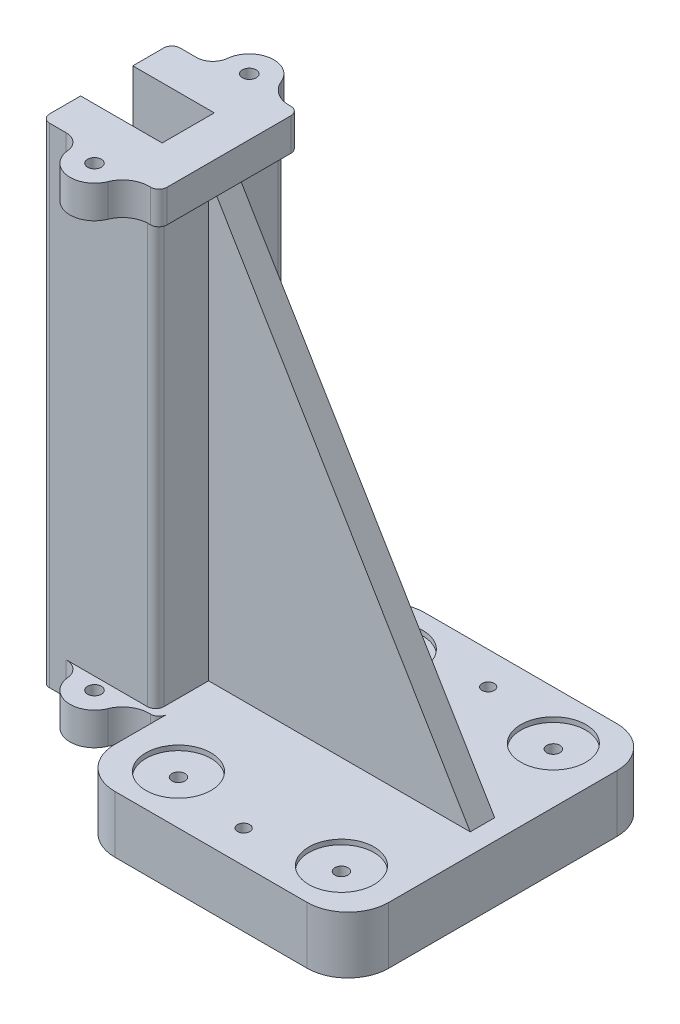
SolidWorks part; units mm, degrees
ref_plane "前视基准面" through (0, 0, 0) normal (0, 0, 1) x (1, 0, 0)
ref_plane "上视基准面" through (0, 0, 0) normal (0, 1, 0) x (1, 0, 0)
ref_plane "右视基准面" through (0, 0, 0) normal (1, 0, 0) x (0, 0, -1)
sketch "草图2" plane through (0, 0, 0) normal (0, 1, 0) x (1, 0, 0)
  line L1 (84, -95) -> (-84, -95)
  line L2 (84, -95) -> (84, 95)
  line L3 (84, 95) -> (-84, 95)
  line L4 (-84, -95) -> (-84, 95)
  line L5 (84, -95) -> (-84, 95) construction
  line L6 (84, 95) -> (-84, -95) construction
  point P0 (0, 0)
  dimension "D1" = 168
  dimension "D2" = 190
extrude "凸台-拉伸1" add sketch "草图2" along normal blind 35
sketch "草图3" plane through (0, 35, 0) normal (0, 1, 0) x (1, 0, 0)
  line L0 (0, 95) -> (0, -95) construction
  line L1 (84, 95) -> (-84, 95) construction
  line L2 (-84, -95) -> (84, -95) construction
  line L3 (-84, 0) -> (84, 0) construction
  line L4 (-84, 95) -> (-84, -95) construction
  line L5 (84, -95) -> (84, 95) construction
  circle A0 centre (0, 75) radius 3.75
  circle A1 centre (0, -75) radius 3.75
  point P16 (0, 0)
  point P17 (0, 0)
  point P18 (0, 0)
  dimension "D1" = 7.5
  dimension "D2" = 150
extrude "切除-拉伸1" cut sketch "草图3" against normal up to next
sketch "草图4" plane through (0, 35, 0) normal (0, 1, 0) x (1, 0, 0)
  line L3 (50, -65) -> (-50, -65) construction
  line L6 (50, -65) -> (50, 65) construction
  line L7 (50, 65) -> (-50, 65) construction
  line L8 (-50, -65) -> (-50, 65) construction
  line L9 (50, -65) -> (-50, 65) construction
  line L10 (50, 65) -> (-50, -65) construction
  circle A4 centre (-50, 65) radius 4
  circle A5 centre (50, 65) radius 4
  circle A6 centre (-50, -65) radius 4
  circle A7 centre (50, -65) radius 4
  point P0 (0, 0)
  dimension "D3" = 8
  dimension "D1" = 130
  dimension "D2" = 100
extrude "切除-拉伸2" cut sketch "草图4" against normal up to next
sketch "草图5" plane through (0, 35, 0) normal (0, 1, 0) x (1, 0, 0)
  circle A0 centre (-50, 65) radius 20
  circle A1 centre (50, 65) radius 20
  circle A2 centre (50, -65) radius 20
  circle A3 centre (-50, -65) radius 20
  dimension "D1" = 40
extrude "切除-拉伸3" cut sketch "草图5" against normal blind 3
fillet "圆角1" radius 25 4 edges at (-84, 17.5, -95) (84, 17.5, -95) (84, 17.5, 95) (-84, 17.5, 95)
ref_plane "基准面1" through (0, 315, 0) normal (0, 1, 0) x (1, 0, 0)
sketch "草图8" plane through (0, 315, 0) normal (0, 1, 0) x (1, 0, 0)
  line L0 (-50, 65) -> (-50, -65) construction
  line L1 (0, 0) -> (-171.4054, 0) construction
  line L2 (-109, -16) -> (-159, -16)
  line L3 (-119, 47.5) -> (-119, -47.5) construction
  line L4 (-109, 16) -> (-109, -16)
  line L5 (-109, 16) -> (-159, 16)
  line L6 (-159, 16) -> (-159, 35)
  line L7 (-84, 70) -> (-84, -70) construction
  line L9 (-84, 38.0172) -> (-84, -38.0172)
  line L13 (-159, -16) -> (-159, -40)
  line L14 (-154, 40) -> (-143.8747, 40)
  line L15 (-143.8747, 40) -> (-74.7829, 40) construction
  line L16 (-154, -40) -> (-143.8747, -40)
  arc A0 (-105.0963, 53.1292) -> (-133.9248, 49) centre (-119, 47.5) ccw
  arc A11 (-159, 35) -> (-154, 40) centre (-154, 35) cw
  arc A12 (-143.8747, 40) -> (-133.9248, 49) centre (-143.8747, 50) ccw
  arc A13 (-84, 38.0172) -> (-89.2482, 43.011) centre (-89, 38.0172) ccw
  arc A14 (-89.2482, 43.011) -> (-105.0963, 53.1292) centre (-90.054, 59.2195) cw
  arc A15 (-84, -38.0172) -> (-89.2482, -43.011) centre (-89, -38.0172) cw
  arc A16 (-89.2482, -43.011) -> (-105.0963, -53.1292) centre (-90.054, -59.2195) ccw
  arc A17 (-105.0963, -53.1292) -> (-133.9248, -49) centre (-119, -47.5) cw
  arc A18 (-143.8747, -40) -> (-133.9248, -49) centre (-143.8747, -50) cw
  arc A19 (-159, -35) -> (-154, -40) centre (-154, -35) ccw
  point P7 (0, 16)
  point P9 (0, -16)
  point P15 (-134, -16)
  point P16 (-104.5565, 51.5478)
  point P20 (-159, 40)
  point P30 (-86.8263, 49)
  point P31 (-84, 42.5366)
  point P32 (-84, 40.0619)
  point P33 (-104.6841, 51.9784)
  point P34 (-84, 38.9071)
  point P37 (0, 0)
  point P39 (-91.6967, 43.1953)
  point P40 (0, 0)
  point P41 (-104.8319, 52.4259)
  point P42 (-91.6226, 58.5844)
  point P54 (-84, -50.4054)
  point P55 (-84, -38.0172)
  dimension "D6" = 30
  dimension "D8" = 5
  dimension "D9" = 10
  dimension "D10" = 5
  dimension "D3" = 59
  dimension "D1" = 32
  dimension "D2" = 50
  dimension "D4" = 10
  dimension "D5" = 95
  dimension "D7" = 80
extrude "凸台-拉伸2" add sketch "草图8" against normal blind 300
sketch "草图10" plane through (0, 35, 0) normal (0, 1, 0) x (1, 0, 0)
  line L0 (-89, 40) -> (-89, -35)
  line L1 (-84, 38.0172) -> (-84, -38.0172) construction
  line L2 (-94, 40) -> (-154, 40)
  line L3 (-94, -40) -> (-154, -40)
  line L4 (0, 0) -> (-24.5816, 0) construction
  line L5 (-159, -16) -> (-159, -35) construction
  line L6 (-159, -16) -> (-159, -35)
  line L7 (-159, 16) -> (-159, 35)
  line L8 (-159, 16) -> (-166.3918, 16)
  line L9 (-166.3918, 16) -> (-166.3918, 67.5934)
  line L10 (-166.3918, 67.5934) -> (-78.897, 67.5934)
  line L12 (-78.897, 67.5934) -> (-78.897, -67.5934)
  line L13 (-159, -16) -> (-166.3918, -16)
  line L14 (-166.3918, -67.5934) -> (-78.897, -67.5934)
  line L15 (-166.3918, -16) -> (-166.3918, -67.5934)
  arc A0 (-159, -35) -> (-154, -40) centre (-154, -35) ccw
  arc A1 (-89, -35) -> (-94, -40) centre (-94, -35) cw
  arc A2 (-89, 35) -> (-94, 40) centre (-94, 35) ccw
  arc A3 (-159, 35) -> (-154, 40) centre (-154, 35) cw
  point P14 (-89, -40)
  point P26 (-78.897, 0)
  dimension "D3" = 5
  dimension "D5" = 5
  dimension "D1" = 5
  dimension "D2" = 80
  dimension "D4" = 80
extrude "切除-拉伸4" cut sketch "草图10" along normal blind 260
sketch "草图11" plane through (0, 0, 0) normal (0, 0, 1) x (1, 0, 0)
  line L0 (-84, 295) -> (71.5, 35)
  line L1 (84, 35) -> (59, 35) construction
  line L2 (-84, 295) -> (-89.2482, 295)
  line L3 (-89.2482, 295) -> (-89.2482, 35)
  line L4 (-89.2482, 35) -> (71.5, 35)
extrude "凸台-拉伸3" add sketch "草图11" along normal mid plane 15
sketch "草图12" plane through (0, 315, 0) normal (0, 1, 0) x (1, 0, 0)
  circle A0 centre (-119, 47.5) radius 4.25
  circle A1 centre (-119, -47.5) radius 4.25
  dimension "D1" = 8.5
extrude "切除-拉伸5" cut sketch "草图12" against normal through all
equation "\"A1L\"= 168"
equation "\"A2L\"= 100"
equation "\"A3L\"= 50"
equation "\"A4L\"= 59"
equation "\"B1L\"= 130"
equation "\"B2L\"= 150"
equation "\"B3L\"= 190"
equation "\"A\"= 40"
equation "\"B\"= 17"
equation "\"D1@草图2\"=\"A1L\""
equation "\"D2@草图2\"=\"B3L\""
equation "\"D2@草图3\"=\"B2L\""
equation "\"D1@草图4\"=\"B1L\""
equation "\"D2@草图4\"=\"A2L\""
equation "\"D1@草图5\"=\"A\""
equation "\"D3@草图8\"=\"A4L\""
